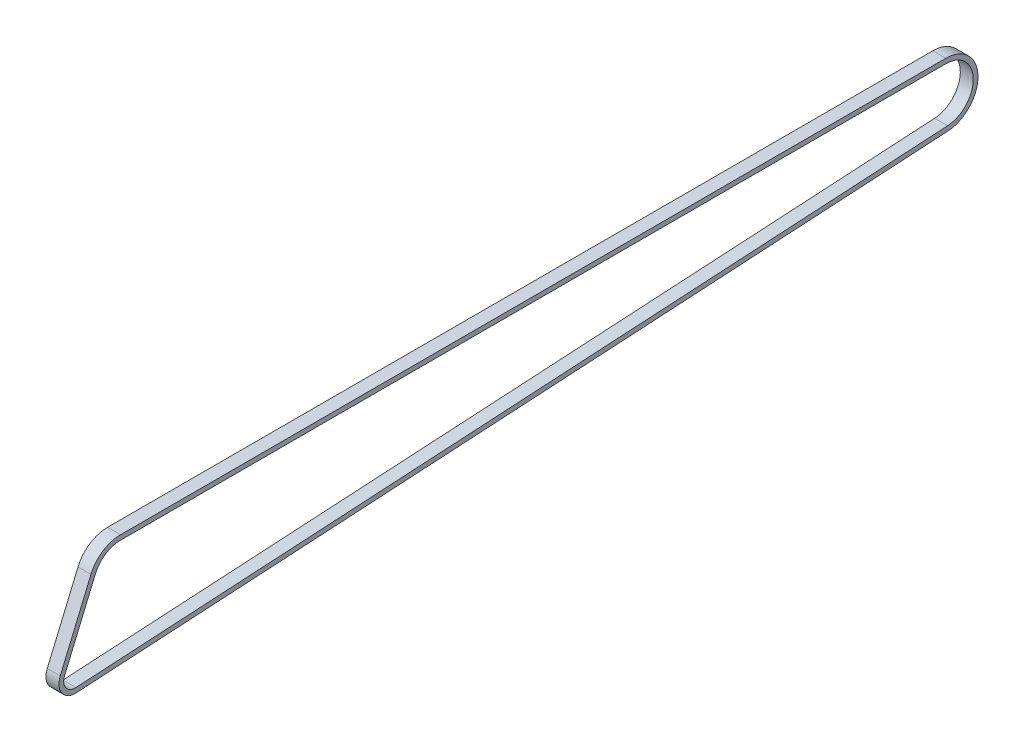
SolidWorks part; units mm, degrees
material "POLYURETHANE (11671)"
ref_plane "Front (1)" through (0, 0, 0) normal (0, 0, 1) x (1, 0, 0)
ref_plane "Top (2)" through (0, 0, 0) normal (0, 1, 0) x (1, 0, 0)
ref_plane "Right (3)" through (0, 0, 0) normal (1, 0, 0) x (0, 0, -1)
ref_axis "X Axis" through (13.5064, 0, 0) along (-1, 0, 0)
ref_axis "Y Axis" through (0, 12.3593, 0) along (0, -1, 0)
ref_axis "Z Axis" through (0, 0, 14.1119) along (0, 0, -1)
sketch "Sketch1" plane through (0, 0, 0) normal (1, 0, 0) x (0, 0, -1)
  line L0 (0.3109, -5.3474) -> (403.88, 18.1162)
  line L1 (403.1457, 43.3949) -> (20.9425, 43.3949)
  line L2 (9.2942, 35.6785) -> (-4.9323, 2.089)
  arc A0 (-4.9323, 2.089) -> (0.3109, -5.3474) centre (0, 0) ccw
  arc A1 (403.88, 18.1162) -> (403.1457, 43.3949) centre (403.1457, 30.7449) ccw
  arc A2 (20.9425, 43.3949) -> (9.2942, 35.6785) centre (20.9425, 30.7449) ccw
  line B0 (0, 0) -> (5.3564, 0) construction
  circle B1 centre (0, 0) radius 5.3564
  line B2 (20.9425, 30.7449) -> (33.5925, 30.7449) construction
  circle B3 centre (20.9425, 30.7449) radius 12.65
  circle B4 centre (403.1457, 30.7449) radius 12.65
sketch_block_instance "Block1-1"
sketch_block "Block1"
sketch_block_instance "Block2-1"
sketch_block "Block2" parameters "D1"=29.7276
sketch_block_instance "Block2-2"
other "Belt1"
ref_plane "Plane1" through (0, 2.089, 4.9323) normal (0, -0.9208, 0.39) x (1, 0, 0)
sketch "Sketch3" plane through (0, 2.089, 4.9323) normal (0, -0.9208, 0.39) x (1, 0, 0)
  line L1 (-3, 2.2) -> (3, 2.2)
  line L2 (-3, 2.2) -> (-3, 0)
  line L3 (-3, 0) -> (3, 0)
  line L4 (3, 2.2) -> (3, 0)
  dimension "D1" = 6
  dimension "D2" = 2.2
sweep "Sweep1" add profiles "Sketch3" path "Sketch1"
